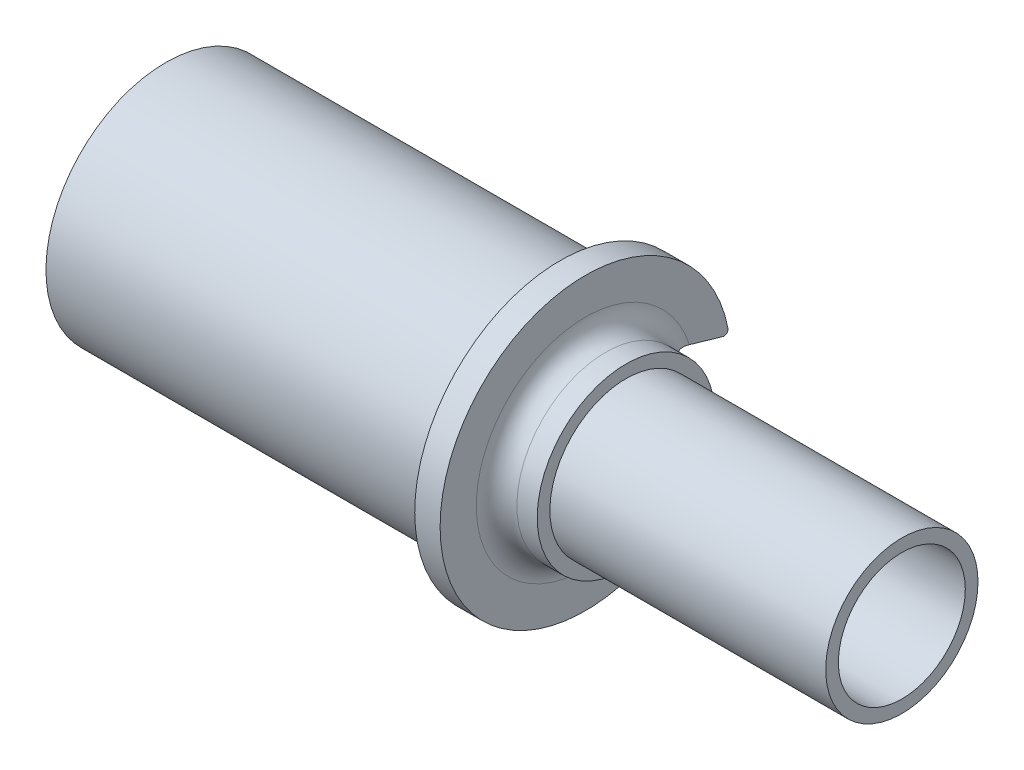
SolidWorks part; units mm, degrees
material "6061-T6 (SS)"
ref_plane "Front Plane" through (0, 0, 0) normal (0, 0, 1) x (1, 0, 0)
ref_plane "Top Plane" through (0, 0, 0) normal (0, 1, 0) x (1, 0, 0)
ref_plane "Right Plane" through (0, 0, 0) normal (1, 0, 0) x (0, 0, -1)
sketch "Sketch1" plane through (0, 0, 0) normal (0, 0, 1) x (1, 0, 0)
  line L0 (0, 0) -> (-16.6687, 0) construction
  line L1 (-6.0506, 3.9687) -> (-6.0506, 4.7625)
  line L2 (-6.0506, 4.7625) -> (-23.3006, 4.7625)
  line L3 (-25.8406, 5.5562) -> (-25.8406, 9.0875)
  line L4 (-25.8406, 9.0875) -> (-27.4281, 9.0875)
  line L5 (-27.4281, 9.0875) -> (-27.4281, 7.5)
  line L6 (-27.4281, 7.5) -> (-52.0781, 7.5)
  line L7 (-52.0781, 7.5) -> (-52.0781, 3.9687)
  line L8 (-52.0781, 3.9687) -> (-6.0506, 3.9687)
  line L9 (-23.3006, 4.7625) -> (-23.3006, 5.5562)
  line L10 (-23.3006, 5.5562) -> (-25.8406, 5.5562)
  line L11 (-52.0781, -4.2228) -> (-52.0781, 4.2227) construction
  line L12 (-34.4281, 15.2446) -> (-34.4281, -15.2446) construction
  dimension "D1" = 7.9375
  dimension "D4" = 15
  dimension "D3" = 9.525
  dimension "D2" = 1.5875
  dimension "D5" = 1.5875
  dimension "D6" = 7
  dimension "D8" = 2.54
  dimension "D9" = 0.7937
  dimension "D7" = 17.25
revolve "Revolve1" add sketch "Sketch1" angle 360 about L0
sketch "Sketch4" plane through (-52.0781, 0, 0) normal (-1, 0, 0) x (0, 0, 1)
  line L0 (-2.6604, 9.1459) -> (0, 0) construction
  arc A0 (-10.2214, 9.1698) -> (3.7082, 13.2217) centre (-6.4003, 22.0034) ccw construction
ref_plane "Plane1" through (0, 0, 0) normal (0, 0.2793, 0.9602) x (0, -0.9602, 0.2793)
sketch "Sketch2" [suppressed] plane through (-6.0506, 0, 0) normal (1, 0, 0) x (0, 0, -1)
  line L0 (1.3441, 3.7342) -> (8.2848, 3.7342)
  line L1 (8.2848, -3.7342) -> (1.3441, -3.7342)
  line L2 (0, 0) -> (14.3216, 0) construction
  circle A0 centre (0, 0) radius 3.9687 construction
  circle A1 centre (0, 0) radius 9.0875 construction
  arc A2 (1.3441, 3.7342) -> (1.3441, -3.7342) centre (0, 0) cw
  arc A3 (8.2848, 3.7342) -> (8.2848, -3.7342) centre (0, 0) cw
  arc A4 (3.6742, 3.7342) -> (3.6742, -3.7342) centre (0, 0) cw construction
  circle A5 centre (5.2387, 0) radius 1.27 construction
  circle A6 centre (4.623, 2.4642) radius 1.27 construction
  circle A7 centre (4.623, -2.4642) radius 1.27 construction
  dimension "D1" = 1.27
  dimension "D2" = 2.54
extrude "Cut-Extrude1" [suppressed] cut sketch "Sketch2" against normal through all both
sketch "Sketch3" plane through (0, 0, 0) normal (0, 0.2793, 0.9602) x (1, 0, 0)
  line L1 (-39.3781, 1.4287) -> (-39.3781, -1.4287)
  line L2 (-36.9969, -3.81) -> (-25.8406, -3.81)
  line L3 (-39.3781, 8.89) -> (-39.3781, -3.81) construction
  line L4 (-25.8406, 3.81) -> (-36.9969, 3.81)
  line L5 (-22.6656, -0.635) -> (-22.6656, 0.635)
  line L6 (-22.6656, 0) -> (0, 0) construction
  line L7 (-52.0781, 3.81) -> (-52.0781, -3.81)
  line L8 (-25.8406, -9.0875) -> (-25.8406, 9.0875) construction
  line L9 (-52.0781, 7.5) -> (-52.0781, -7.5) construction
  line L10 (-52.0781, -3.81) -> (-48.9031, -3.81)
  line L11 (-47.3156, -2.2225) -> (-47.3156, 2.2225)
  line L12 (-48.9031, 3.81) -> (-52.0781, 3.81)
  arc A1 (-25.8406, -3.81) -> (-22.6656, -0.635) centre (-25.8406, -0.635) ccw
  arc A2 (-22.6656, 0.635) -> (-25.8406, 3.81) centre (-25.8406, 0.635) ccw
  arc A3 (-39.3781, -1.4287) -> (-36.9969, -3.81) centre (-36.9969, -1.4287) ccw
  arc A4 (-39.3781, 1.4287) -> (-36.9969, 3.81) centre (-36.9969, 1.4287) cw
  arc A5 (-48.9031, -3.81) -> (-47.3156, -2.2225) centre (-48.9031, -2.2225) ccw
  arc A6 (-47.3156, 2.2225) -> (-48.9031, 3.81) centre (-48.9031, 2.2225) ccw
  dimension "D1" = 7.62
  dimension "D2" = 3.175
  dimension "D3" = 2.3813
  dimension "D4" = 1.5875
  dimension "D5" = 3.175
extrude "Cut-Extrude2" cut sketch "Sketch3" against normal up to next
fillet "Fillet1" radius 0.254 12 edges at (-26.6344, 1.3541, -8.9861) (-26.6344, -5.9627, -6.8578) (-32.2125, -5.4627, -5.1389) (-32.2125, 1.854, -7.2672) (-38.8575, -4.7289, -5.8213) (-39.3781, -2.0948, -7.2015) (-38.3557, 1.3802, -7.3719) (-50.4906, 1.854, -7.2672) (-47.6952, 1.2356, -7.3975) (-47.3156, -2.0948, -7.2015) (-48.0025, -5.2376, -5.3682) (-50.4906, -5.4627, -5.1389)
fillet "Fillet2" radius 0.254 3 edges at (-27.4281, 2.0498, -7.0776) (-27.4281, -5.5262, -4.8739) (-27.4281, 2.0948, 7.2015)
fillet "Fillet3" radius 1.27 1 edges at (-25.8406, 1.5519, 5.3351)
ref_axis "Axis1" through (-54.3795, 0, 0) along (1, 0, 0)
ref_plane "Plane2" through (0, 0, 0) normal (0, -0.2793, -0.9602) x (1, 0, 0)
sketch "Sketch6" plane through (-52.0781, 0, 0) normal (-1, 0, 0) x (0, 0, 1)
  line L0 (-5.5155, 2.3636) -> (-3.3873, -4.9532)
  line L1 (-5.5155, 2.3636) -> (-11.0029, 0.7674)
  line L2 (-3.3873, -4.9532) -> (-8.8746, -6.5494)
  line L3 (-11.0029, 0.7674) -> (-8.8746, -6.5494)
  line L4 (-6.8244, 1.9828) -> (-2.1312, 3.348) construction
  line L5 (-4.6961, -5.3339) -> (-0.0029, -3.9687) construction
  line L6 (-6.8244, 1.9828) -> (-2.1312, 3.348) construction
extrude "Cut-Extrude3" cut sketch "Sketch6" against normal up to next
equation "\"bearing1\"=0.273438"
equation "\"D1@Sketch1\"=5/16"
equation "\"D4@Sketch1\"=15mm"
equation "\"D6@Sketch1\"=7mm"
equation "\"D7@Sketch1\"=17.25mm"
